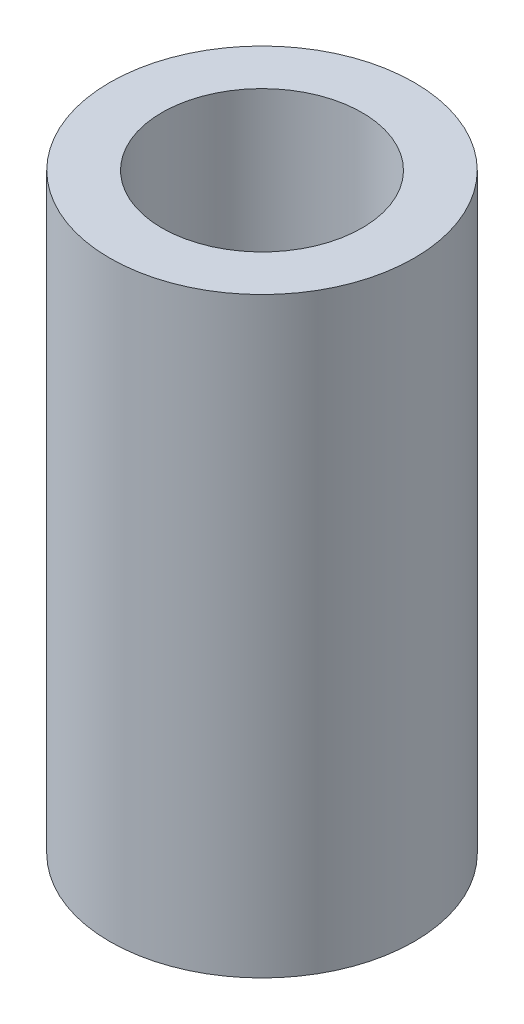
SolidWorks part; units mm, degrees
material "Amonium Percholorate"
ref_plane "Front Plane" through (0, 0, 0) normal (0, 0, 1) x (1, 0, 0)
ref_plane "Top Plane" through (0, 0, 0) normal (0, 1, 0) x (1, 0, 0)
ref_plane "Right Plane" through (0, 0, 0) normal (1, 0, 0) x (0, 0, -1)
sketch "Sketch2" plane through (0, 0, 0) normal (0, 1, 0) x (1, 0, 0)
  circle A0 centre (0, 0) radius 44.831
  circle A1 centre (0, 0) radius 29.4725
  dimension "D1" = 89.662
extrude "Extrude1" add sketch "Sketch2" along normal blind 174.3333
